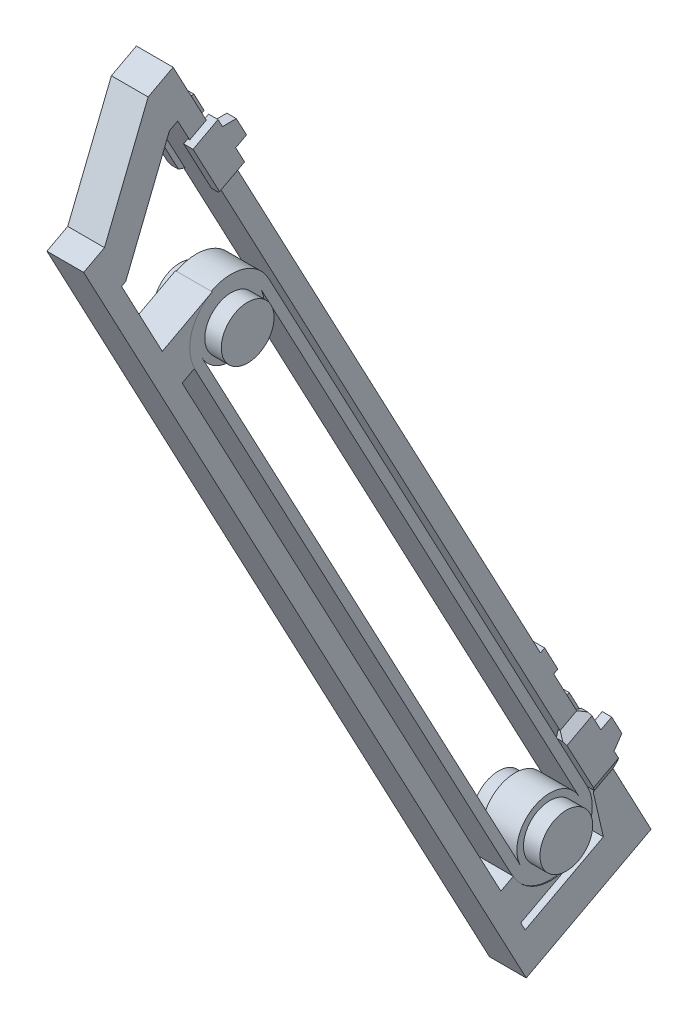
SolidWorks part; units mm, degrees
ref_plane "Front Plane" through (0, 0, 0) normal (0, 0, 1) x (1, 0, 0)
ref_plane "Top Plane" through (0, 0, 0) normal (0, 1, 0) x (1, 0, 0)
ref_plane "Right Plane" through (0, 0, 0) normal (1, 0, 0) x (0, 0, -1)
sketch "Sketch2" plane through (0, 0, 0) normal (1, 0, 0) x (0, 0, -1)
  line L0 (0, 0) -> (132.4421, 70.4207)
  line L1 (132.4421, 70.4207) -> (-374.5871, 1024.0041)
  line L2 (0, 0) -> (-469.4716, 882.9476)
  line L3 (0, 0) -> (-54.7132, 0) construction
  line L4 (-374.5871, 1024.0041) -> (-401.0756, 1009.92)
  line L5 (-401.0756, 1009.92) -> (-447.3979, 894.6844)
  line L6 (-447.3979, 894.6844) -> (-469.4716, 882.9476)
  line L7 (-369.7115, 972.2332) -> (-378.5409, 967.5385)
  line L8 (-378.5409, 967.5385) -> (-424.8632, 852.3029)
  line L9 (-424.8632, 852.3029) -> (-429.278, 849.9555)
  line L10 (-401.0756, 1009.92) -> (-378.5409, 967.5385) construction
  line L11 (-447.3979, 894.6844) -> (-424.8632, 852.3029) construction
  line L12 (-1.1199, 44.7073) -> (81.8092, 88.8015)
  line L13 (81.8092, 88.8015) -> (67.836, 149.3261)
  line L15 (67.836, 149.3261) -> (-369.7115, 972.2332)
  line L16 (-429.278, 849.9555) -> (-1.1199, 44.7073)
  dimension "D1" = 62
  dimension "D2" = 1000
  dimension "D3" = 150
  dimension "D4" = 1080
  dimension "D5" = 30
  dimension "D6" = 48
  dimension "D7" = 25
  dimension "D8" = 75
  dimension "D9" = 40
  dimension "D10" = 20
  dimension "D11" = 60
  dimension "D12" = 20
extrude "Boss-Extrude1" add sketch "Sketch2" along normal mid plane 39
sketch "Sketch3" plane through (0, 0, 0) normal (1, 0, 0) x (0, 0, -1)
  line L0 (132.4421, 70.4207) -> (-374.5871, 1024.0041) construction
  line L1 (0, 0) -> (132.4421, 70.4207) construction
  circle A0 centre (26.036, 121.4377) radius 28
  circle A1 centre (-311.9835, 757.16) radius 28
  dimension "D1" = 56
  dimension "D2" = 70
  dimension "D3" = 95
  dimension "D4" = 70
  dimension "D5" = 720
extrude "Boss-Extrude2" add sketch "Sketch3" along normal mid plane 72 separate body
sketch "Sketch4" plane through (0, 0, 0) normal (1, 0, 0) x (0, 0, -1)
  circle A0 centre (26.036, 121.4377) radius 35
  circle A1 centre (-311.9835, 757.16) radius 35
  dimension "D1" = 70
extrude "Boss-Extrude3" add sketch "Sketch4" along normal mid plane 37
sketch "Sketch5" plane through (0, 0, 0) normal (1, 0, 0) x (0, 0, -1)
  line L0 (-281.0804, 773.5915) -> (56.9392, 137.8693)
  line L1 (-342.8867, 740.7285) -> (-4.8672, 105.0062)
  line L2 (-272.2509, 778.2862) -> (65.7687, 142.564)
  line L3 (-351.7162, 736.0338) -> (-13.6966, 100.3115)
  circle A0 centre (26.036, 121.4377) radius 35 construction
  circle A1 centre (-311.9835, 757.16) radius 35 construction
  arc A2 (-4.8672, 105.0062) -> (56.9392, 137.8693) centre (26.036, 121.4377) ccw
  arc A3 (-281.0804, 773.5915) -> (-342.8867, 740.7285) centre (-311.9835, 757.16) ccw
  arc A4 (-13.6966, 100.3115) -> (65.7687, 142.564) centre (26.036, 121.4377) ccw
  arc A5 (-272.2509, 778.2862) -> (-351.7162, 736.0338) centre (-311.9835, 757.16) ccw
  dimension "D1" = 10
extrude "Boss-Extrude4" add sketch "Sketch5" along normal mid plane 37
sketch "Sketch6" plane through (19.5, 0, 0) normal (1, 0, 0) x (0, 0, -1)
  line L0 (-361.4505, 946.0463) -> (-334.962, 960.1304)
  line L3 (-306.7937, 907.1536) -> (-333.2822, 893.0694)
  line L4 (-333.2822, 893.0694) -> (-361.4505, 946.0463)
  line L5 (-334.962, 960.1304) -> (-330.2673, 951.3009)
  line L6 (-330.2673, 951.3009) -> (-315.5439, 951.3009)
  line L7 (-315.5439, 951.3009) -> (-304.7049, 930.9156)
  line L8 (-304.7049, 930.9156) -> (-316.1832, 924.8125)
  line L9 (-316.1832, 924.8125) -> (-306.7937, 907.1536)
  line L10 (132.4421, 70.4207) -> (-374.5871, 1024.0041) construction
  line L11 (-374.5871, 1024.0041) -> (-401.0756, 1009.92) construction
  line L12 (67.836, 149.3261) -> (-369.7115, 972.2332) construction
  dimension "D1" = 75
  dimension "D2" = 5
  dimension "D3" = 5
  dimension "D4" = 13
  dimension "D5" = 40
  dimension "D6" = 20
  dimension "D7" = 10
extrude "Boss-Extrude5" add sketch "Sketch6" along normal blind 8 and the other way blind 2
mirror "Mirror1" about plane through (0, 0, 0) normal (1, 0, 0) of "Boss-Extrude5"
ref_plane "Plane1" through (0, 88.2948, 46.9472) normal (0, -0.8829, -0.4695) x (-1, 0, 0)
ref_plane "Plane2" through (0, 487.8285, 259.383) normal (0, -0.8829, -0.4695) x (-1, 0, 0)
mirror "Mirror2" about plane through (0, 487.8285, 259.383) normal (0, -0.8829, -0.4695) of "Mirror1", "Boss-Extrude5"
chamfer "Chamfer1" distance 8 angle 45 12 edges at (18.5, 895.4168, 328.8674) (19.5, 900.1115, 320.038) (18.5, 904.8062, 311.2085) (-18.5, 202.3029, -39.6677) (-19.5, 206.9976, -48.4972) (-18.5, 211.6923, -57.3267) (18.5, 202.3029, -39.6677) (19.5, 206.9976, -48.4972) (18.5, 211.6923, -57.3267) (-18.5, 895.4168, 328.8674) (-19.5, 900.1115, 320.038) (-18.5, 904.8062, 311.2085)
chamfer "Chamfer2" distance 8 angle 60 6 edges at (-18.5, 149.3261, -67.836) (-19.5, 154.0208, -76.6655) (-18.5, 158.7155, -85.495) (18.5, 158.7155, -85.495) (19.5, 154.0208, -76.6655) (18.5, 149.3261, -67.836) first distance on face at (-20.5, 154.0208, -76.6655) first distance on face at (20.5, 154.0208, -76.6655)
sketch "Sketch7" plane through (19.5, 0, 0) normal (1, 0, 0) x (0, 0, -1)
  line L0 (47.1622, 81.7051) -> (-23.4736, 44.1474)
  line L1 (-429.278, 849.9555) -> (-1.1199, 44.7073) construction
  line L2 (-23.4736, 44.1474) -> (-44.5998, 83.88)
  line L3 (-44.5998, 83.88) -> (-13.6966, 100.3115)
  line L5 (-333.1097, 796.8927) -> (-403.7455, 759.3349)
  line L6 (-403.7455, 759.3349) -> (-382.6193, 719.6023)
  line L7 (-382.6193, 719.6023) -> (-351.7162, 736.0338)
  line L8 (-469.4716, 882.9476) -> (0, 0) construction
  arc A0 (-13.6966, 100.3115) -> (65.7687, 142.564) centre (26.036, 121.4377) ccw construction
  arc A1 (-272.2509, 778.2862) -> (-351.7162, 736.0338) centre (-311.9835, 757.16) ccw construction
  arc A2 (-13.6966, 100.3115) -> (47.1622, 81.7051) centre (26.036, 121.4377) ccw
  arc A3 (-333.1097, 796.8927) -> (-351.7162, 736.0338) centre (-311.9835, 757.16) ccw
  line M33 (-1.1199, 44.7073) -> (-429.278, 849.9555)
extrude "Boss-Extrude6" add sketch "Sketch7" against normal up to surface (39 mm away) contours A2 L3 L0 M33 | A3 L5 L7 M33 up to face at (-19.5, 615.3451, 225.9465)
sketch "Sketch8" plane through (0, 70.4207, -132.4421) normal (0, 0.4695, -0.8829) x (-1, 0, 0)
  line L0 (-19.5, 168) -> (-19.5, 937) construction
  line L1 (-19.5, 250) -> (19.5, 250)
  line L2 (-19.5, 250) -> (-19.5, 220)
  line L3 (-19.5, 220) -> (19.5, 220)
  line L4 (19.5, 250) -> (19.5, 220)
  line L5 (19.5, 168) -> (19.5, 937) construction
  line L6 (-19.5, 0) -> (19.5, 0) construction
  dimension "D1" = 30
  dimension "D2" = 220
extrude "Boss-Extrude7" add sketch "Sketch8" along normal mid plane 10
